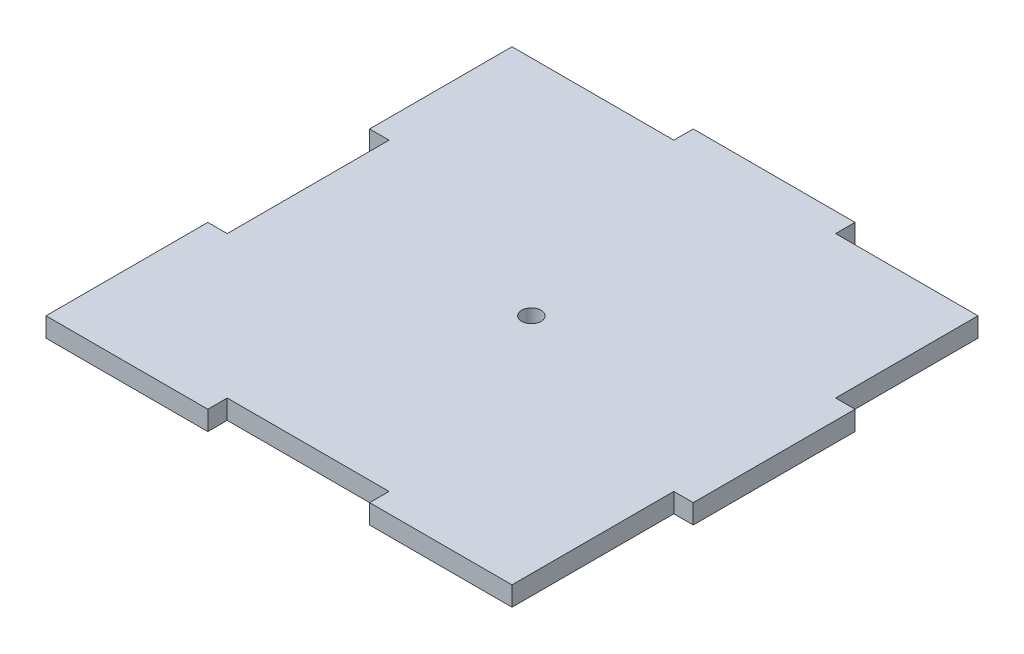
SolidWorks part; units mm, degrees
ref_plane "Front Plane" through (0, 0, 0) normal (0, 0, 1) x (1, 0, 0)
ref_plane "Top Plane" through (0, 0, 0) normal (0, 1, 0) x (1, 0, 0)
ref_plane "Right Plane" through (0, 0, 0) normal (1, 0, 0) x (0, 0, -1)
sketch "Sketch1" plane through (0, 0, 0) normal (0, 1, 0) x (1, 0, 0)
  line L0 (-72, 28) -> (-66, 28)
  line L1 (-72, -72) -> (72, -72)
  line L2 (-72, -72) -> (-72, 72)
  line L3 (-72, 72) -> (72, 72)
  line L4 (72, -72) -> (72, 72)
  line L5 (-72, -72) -> (72, 72) construction
  line L6 (-72, 72) -> (72, -72) construction
  line L7 (-66, 28) -> (-66, -22)
  line L8 (28, -72) -> (28, -66)
  line L9 (-22, 72) -> (-22, 78)
  line L10 (-22, 78) -> (28, 78)
  line L11 (28, 72) -> (28, 78)
  line L12 (72, 28) -> (78, 28)
  line L13 (78, 28) -> (78, -22)
  line L14 (-22, -72) -> (-22, -66)
  line L15 (-22, -66) -> (28, -66)
  line L16 (3, 78) -> (3, -72) construction
  line L17 (-72, 3) -> (78, 3) construction
  line L18 (72, -22) -> (78, -22)
  line L19 (-72, -22) -> (-66, -22)
  circle A0 centre (3, 3) radius 3
  point P0 (0, 0)
  point P22 (3, 3)
  point P27 (3, 3)
  point P40 (3, -66)
  point P45 (-66, 3)
  dimension "D4" = 6
  dimension "D1" = 144
  dimension "D2" = 25
  dimension "D3" = 6
extrude "Boss-Extrude1" add sketch "Sketch1" along normal blind 6 contours L19 L2 L1 L14 L15 L8 L4 L3 L0 L7 | L3 L11 L10 L9 | L4 L18 L13 L12 region at (-69.9635, 0, -50) region at (3, 0, -75) region at (75, 0, -3)
